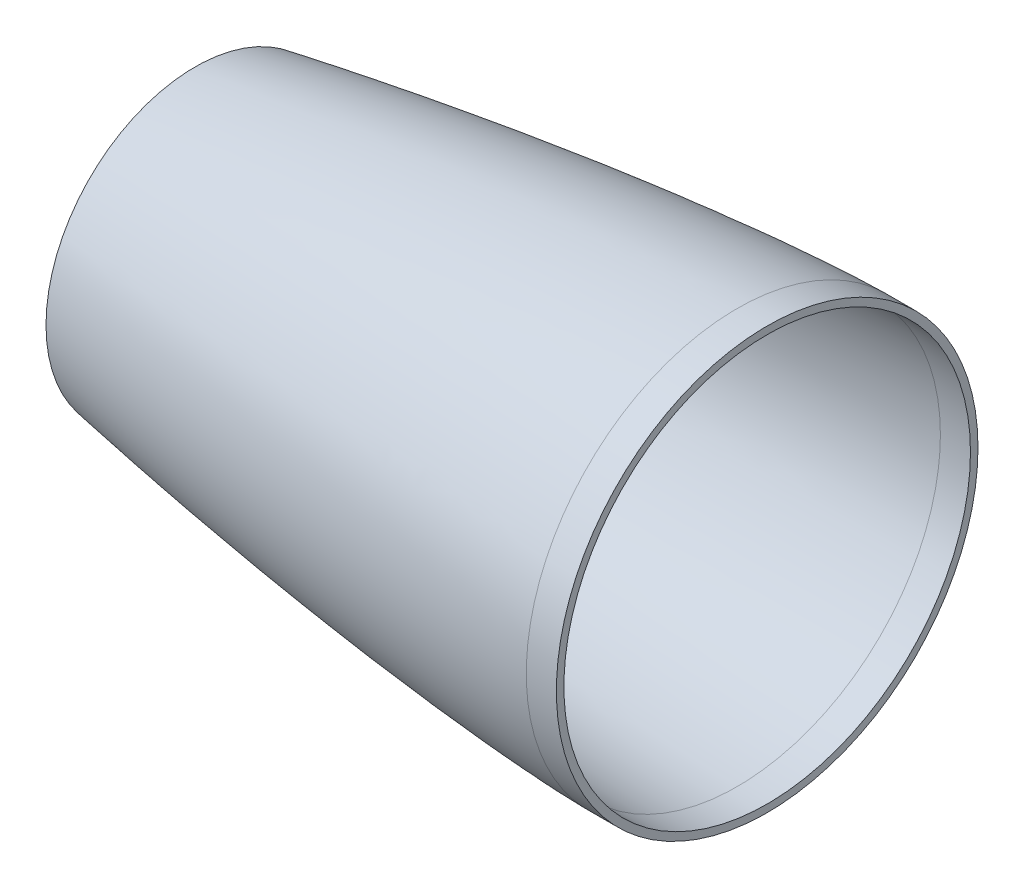
SolidWorks part; units mm, degrees
ref_plane "Front Plane" through (0, 0, 0) normal (0, 0, 1) x (1, 0, 0)
ref_plane "Top Plane" through (0, 0, 0) normal (0, 1, 0) x (1, 0, 0)
ref_plane "Right Plane" through (0, 0, 0) normal (1, 0, 0) x (0, 0, -1)
sketch "Sketch1" plane through (0, 0, 0) normal (0, 0, 1) x (1, 0, 0)
  line L0 (0, 0) -> (457.2, 0) construction
  line L1 (0, 0) -> (0, 88.9) construction
  line L2 (457.2, 88.9151) -> (457.2, 0) construction
  line L3 (457.2, 0) -> (0, 0)
  line L5 (457.2, 0) -> (469.9, 0)
  line L7 (457.2, 88.9151) -> (469.9, 88.9151)
  line L8 (469.9, 0) -> (469.9, 88.9151)
  spline S0 degree 4 poles (0, 0) (0.0023, 0.0117) (0.0082, 0.0346) (0.0259, 0.0787) (0.0695, 0.163) (0.1339, 0.2631) (0.2191, 0.3779) (0.3369, 0.5207) (0.5082, 0.71) (0.7967, 0.9964) (1.2973, 1.4371) (2.1712, 2.1158) (3.7004, 3.1565) (6.4155, 4.7689) (11.1356, 7.1992) (18.8819, 10.6607) (32.1609, 15.8309) (51.2281, 22.2453) (75.2291, 29.3426) (102.987, 36.6637) (131.6184, 43.5191) (160.3731, 49.8355) (189.2264, 55.6835) (218.1627, 61.1047) (247.1713, 66.1244) (276.2447, 70.7536) (305.3776, 74.9923) (334.5665, 78.8281) (363.8087, 82.2339) (389.4414, 84.7941) (411.4449, 86.6328) (428.6333, 87.7894) (439.7384, 88.3858) (448.4262, 88.7338) (453.4393, 88.8671) (455.9463, 88.9096) (457.2, 88.9151) knots 0 0 0 0 0 0.000101 0.000202 0.000405 0.000809 0.001116 0.001422 0.001985 0.002988 0.004584 0.007113 0.011426 0.01877 0.031526 0.052412 0.083828 0.140383 0.203215 0.266046 0.328877 0.391708 0.454539 0.51737 0.580202 0.643033 0.705864 0.768695 0.831526 0.894357 0.925773 0.957189 0.978594 0.989297 1 1 1 1 1 construction
  spline S1 degree 4 poles (0, 0) (0.0023, 0.0117) (0.0082, 0.0346) (0.0259, 0.0787) (0.0695, 0.163) (0.1339, 0.2631) (0.2191, 0.3779) (0.3369, 0.5207) (0.5082, 0.71) (0.7967, 0.9964) (1.2973, 1.4371) (2.1712, 2.1158) (3.7004, 3.1565) (6.4155, 4.7689) (11.1356, 7.1992) (18.8819, 10.6607) (32.1609, 15.8309) (51.2281, 22.2453) (75.2291, 29.3426) (102.987, 36.6637) (131.6184, 43.5191) (160.3731, 49.8355) (189.2264, 55.6835) (218.1627, 61.1047) (247.1713, 66.1244) (276.2447, 70.7536) (305.3776, 74.9923) (334.5665, 78.8281) (363.8087, 82.2339) (389.4414, 84.7941) (411.4449, 86.6328) (428.6333, 87.7894) (439.7384, 88.3858) (448.4262, 88.7338) (453.4393, 88.8671) (455.9463, 88.9096) (457.2, 88.9151) knots 0 0 0 0 0 0.000101 0.000202 0.000405 0.000809 0.001116 0.001422 0.001985 0.002988 0.004584 0.007113 0.011426 0.01877 0.031526 0.052412 0.083828 0.140383 0.203215 0.266046 0.328877 0.391708 0.454539 0.51737 0.580202 0.643033 0.705864 0.768695 0.831526 0.894357 0.925773 0.957189 0.978594 0.989297 1 1 1 1 1
  dimension "D1" = 457.2
  dimension "D2" = 88.9
  dimension "D3" = 12.7
revolve "Revolve1" add sketch "Sketch1" angle 360 about L3
shell "Shell1" thickness 3.175 removed face at (469.9, 0, -88.9151)
sketch "Sketch2" plane through (0, 0, 0) normal (1, 0, 0) x (0, 0, -1)
  circle A0 centre (0, 0) radius 173.4282
extrude "Cut-Extrude2" cut sketch "Sketch2" along normal blind 228.6
